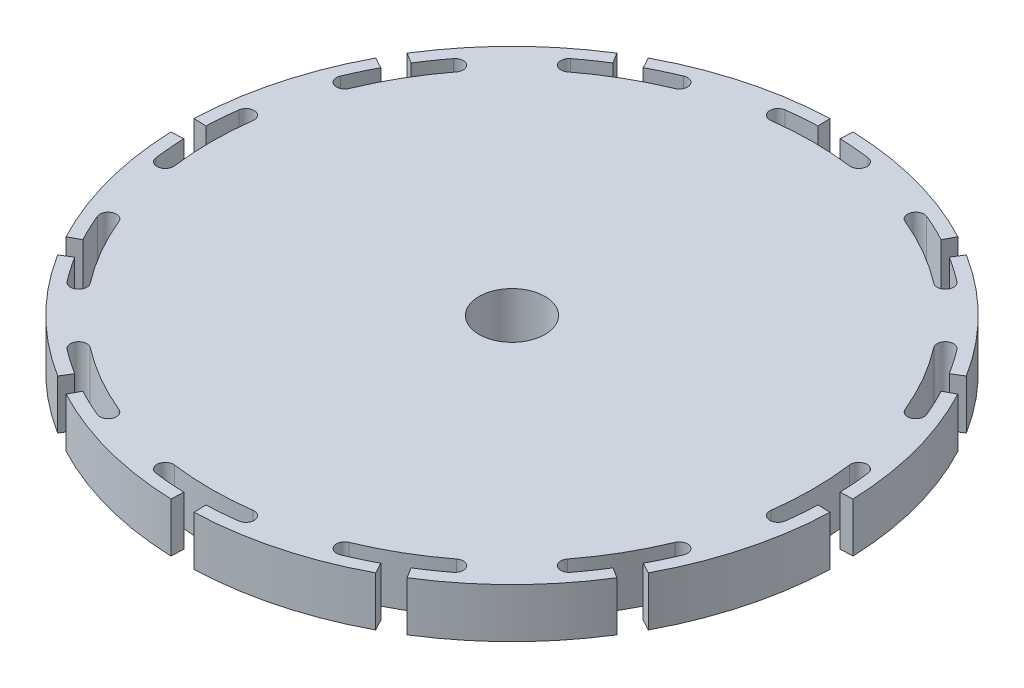
SolidWorks part; units mm, degrees
ref_plane "Front Plane" through (0, 0, 0) normal (0, 0, 1) x (1, 0, 0)
ref_plane "Top Plane" through (0, 0, 0) normal (0, 1, 0) x (1, 0, 0)
ref_plane "Right Plane" through (0, 0, 0) normal (1, 0, 0) x (0, 0, -1)
sketch "Sketch1" plane through (0, 0, 0) normal (0, 1, 0) x (1, 0, 0)
  circle A0 centre (0, 0) radius 40
  dimension "D1" = 80
sketch "Sketch2" plane through (0, 0, 0) normal (0, 1, 0) x (1, 0, 0)
  line L0 (0, 0) -> (0, 40) construction
  line L1 (-1.396, 39.9756) -> (0, 0) construction
  line L2 (0, 0) -> (-5.221, 39.6578) construction
  line L3 (-1.396, 39.9756) -> (-1.3436, 38.4765)
  line L4 (0, 0) -> (5.221, 39.6578) construction
  line L5 (1.396, 39.9756) -> (0, 0) construction
  line L6 (1.396, 39.9756) -> (1.3436, 38.4765)
  arc A0 (4.7642, 36.1877) -> (-4.7642, 36.1877) centre (0, 0) ccw
  circle A1 centre (0, 0) radius 40 construction
  arc A2 (-1.396, 39.9756) -> (1.396, 39.9756) centre (0, 0) cw
  arc A3 (-1.3436, 38.4765) -> (-5.0253, 38.1706) centre (0, 0) ccw
  arc A4 (-4.7642, 36.1877) -> (-5.0253, 38.1706) centre (-4.8947, 37.1792) cw
  arc A5 (4.7642, 36.1877) -> (5.0253, 38.1706) centre (4.8947, 37.1792) ccw
  arc A6 (1.3436, 38.4765) -> (5.0253, 38.1706) centre (0, 0) cw
  point P130 (0, 0)
  dimension "D1" = 15
  dimension "D2" = 2
  dimension "D4" = 1.5
  dimension "D3" = 4
sketch "Sketch3" plane through (0, 0, 0) normal (0, 1, 0) x (1, 0, 0)
  circle A0 centre (0, 0) radius 4
  dimension "D1" = 8
extrude "Wheel Blank" add sketch "Sketch1" along normal blind 6
extrude "T-Slot" cut sketch "Sketch2" along normal through all
pattern_circular "CirPattern" count 12 over 360 about axis through (0, 6, 0) along (0, -1, 0) of "T-Slot"
extrude "Center Hole" cut sketch "Sketch3" along normal blind 6
